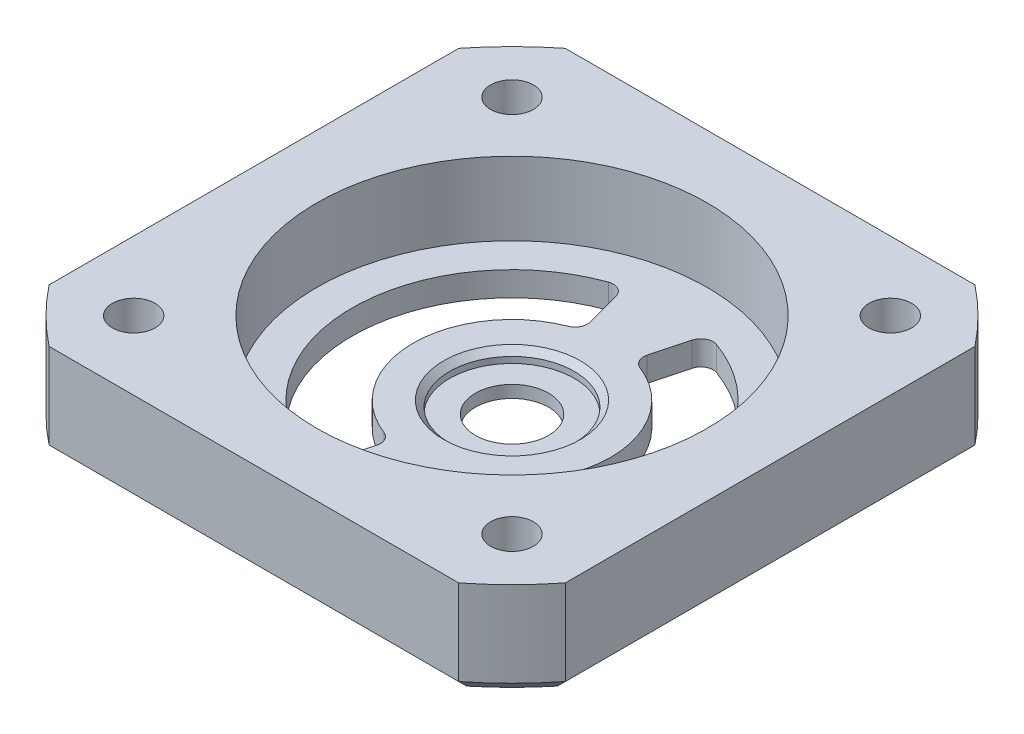
SolidWorks part; units mm, degrees
ref_plane "Front Plane" through (0, 0, 0) normal (0, 0, 1) x (1, 0, 0)
ref_plane "Top Plane" through (0, 0, 0) normal (0, 1, 0) x (1, 0, 0)
ref_plane "Right Plane" through (0, 0, 0) normal (1, 0, 0) x (0, 0, -1)
sketch "Sketch2" plane through (0, 0, 0) normal (0, 1, 0) x (1, 0, 0)
  line L1 (-21.15, 21.15) -> (21.15, 21.15)
  line L2 (-21.15, 21.15) -> (-21.15, -21.15)
  line L3 (-21.15, -21.15) -> (21.15, -21.15)
  line L4 (21.15, 21.15) -> (21.15, -21.15)
  line L5 (-21.15, 21.15) -> (21.15, -21.15) construction
  line L6 (-21.15, -21.15) -> (21.15, 21.15) construction
  point P0 (0, 0)
  dimension "D1" = 42.3
extrude "Boss-Extrude1" add sketch "Sketch2" along normal blind 8
sketch "Sketch5" plane through (0, 8, 0) normal (0, 1, 0) x (1, 0, 0)
  circle A0 centre (0, 0) radius 27
  circle A1 centre (0, 0) radius 29.9106
  dimension "D1" = 54
extrude "Cut-Extrude4" cut sketch "Sketch5" against normal through all
sketch "Sketch6" plane through (0, 8, 0) normal (0, 1, 0) x (1, 0, 0)
  circle A2 centre (0, 0) radius 16
  circle A3 centre (0, 0) radius 10 construction
  dimension "D1" = 32
  dimension "D5" = 20
extrude "Cut-Extrude7" cut sketch "Sketch6" against normal offset from surface (7 mm away) 1 up to face at (0, 0, 0)
sketch "Sketch8" plane through (0, 1, 0) normal (0, 1, 0) x (1, 0, 0)
  circle A0 centre (0, 0) radius 5.1
  circle A2 centre (0, 0) radius 16
  circle A3 centre (0, 0) radius 16
  dimension "D1" = 10.2
  dimension "D2" = 0
extrude "Boss-Extrude3" add sketch "Sketch8" along normal blind 1
sketch "Sketch9" plane through (0, 2, 0) normal (0, 1, 0) x (1, 0, 0)
  line L0 (3.3905, 12.6536) -> (2.0964, 7.824)
  line L1 (3.3905, -12.6536) -> (2.0964, -7.824)
  line L2 (2.0964, -7.824) -> (0, 0) construction
  line L3 (2.0964, 7.824) -> (0, 0) construction
  line L4 (-21.15, 16.7833) -> (-21.15, -16.7833) construction
  line L5 (0, -4.4) -> (0, 4.4) construction
  line L6 (-2.0964, 7.824) -> (0, 0) construction
  line L7 (-2.0964, -7.824) -> (0, 0) construction
  line L8 (-3.3905, -12.6536) -> (-2.0964, -7.824)
  line L9 (-3.3905, 12.6536) -> (-2.0964, 7.824)
  arc A0 (3.3905, 12.6536) -> (3.3905, -12.6536) centre (0, 0) cw
  circle A1 centre (0, 0) radius 5.1 construction
  arc A2 (2.0964, 7.824) -> (2.0964, -7.824) centre (0, 0) cw
  arc A3 (-2.0964, 7.824) -> (-2.0964, -7.824) centre (0, 0) ccw
  arc A4 (-3.3905, 12.6536) -> (-3.3905, -12.6536) centre (0, 0) ccw
  point P5 (2.1209, 7.6847)
  dimension "D1" = 15
  dimension "D4" = 3
  dimension "D2" = 15
  dimension "D3" = 5
extrude "Cut-Extrude8" cut sketch "Sketch9" against normal through all
fillet "Fillet1" radius 1 8 edges at (-3.3905, 1, 12.6536) (-2.0964, 1, -7.824) (-2.0964, 1, 7.824) (-3.3905, 1, -12.6536) (2.0964, 1, 7.824) (2.0964, 1, -7.824) (3.3905, 1, 12.6536) (3.3905, 1, -12.6536)
sketch "Sketch10" plane through (0, 1, 0) normal (0, 1, 0) x (1, 0, 0)
  circle A0 centre (0, 0) radius 3
  dimension "D1" = 6
extrude "Cut-Extrude9" cut sketch "Sketch10" against normal through all
sketch "Sketch7" plane through (0, 8, 0) normal (0, 1, 0) x (1, 0, 0)
  line L1 (-15.5, 15.5) -> (15.5, 15.5) construction
  line L2 (-15.5, 15.5) -> (-15.5, -15.5) construction
  line L3 (-15.5, -15.5) -> (15.5, -15.5) construction
  line L4 (15.5, 15.5) -> (15.5, -15.5) construction
  line L5 (-15.5, 15.5) -> (15.5, -15.5) construction
  line L6 (-15.5, -15.5) -> (15.5, 15.5) construction
  circle A0 centre (-15.5, 15.5) radius 1.75
  circle A1 centre (15.5, 15.5) radius 1.75
  circle A2 centre (15.5, -15.5) radius 1.75
  circle A3 centre (-15.5, -15.5) radius 1.75
  point P0 (0, 0)
  point P16 (0, 0)
  dimension "D3" = 3.5
  dimension "D1" = 31
  dimension "D2" = 31
  dimension "D4" = 4
extrude "Cut-Extrude6" cut sketch "Sketch7" against normal through all
chamfer "Chamfer4" distance 1 angle 45 8 edges at (19.0919, 0, 19.0919) (0, 0, 21.15) (-19.0919, 0, 19.0919) (-21.15, 0, 0) (-19.0919, 0, -19.0919) (0, 0, -21.15) (19.0919, 0, -19.0919) (21.15, 0, 0)
chamfer "Chamfer5" distance 2 angle 45 4 edges at (-15.5, 0, -13.75) (15.5, 0, -13.75) (15.5, 0, 17.25) (-15.5, 0, 17.25)
chamfer "Chamfer6" distance 0.5 angle 45 1 edges at (0, 2, 5.1)
